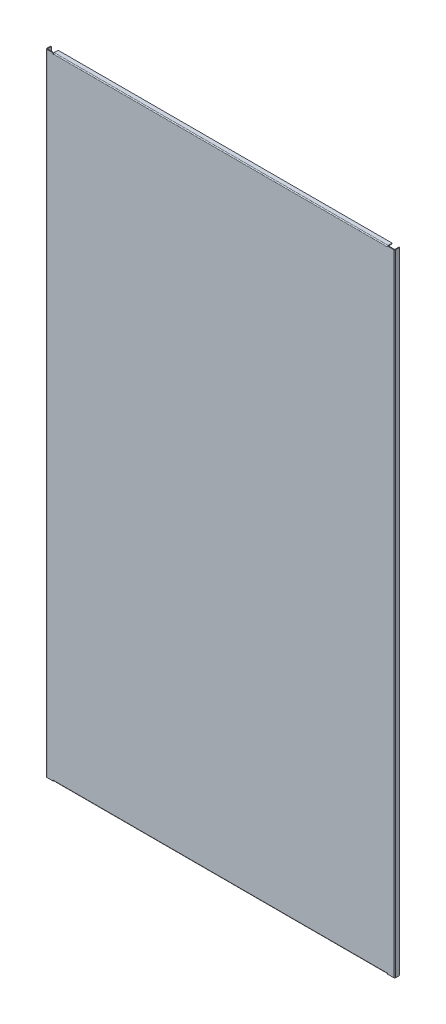
SolidWorks part; units mm, degrees
note: The reader was unsure of these and kept them because the rebuilt part matched: flange length of "Ребро-кромка1", "Ребро-кромка2".
material "AISI 1020"
ref_plane "Спереди" through (0, 0, 0) normal (0, 0, 1) x (1, 0, 0)
ref_plane "Сверху" through (0, 0, 0) normal (0, 1, 0) x (1, 0, 0)
ref_plane "Справа" through (0, 0, 0) normal (1, 0, 0) x (0, 0, -1)
sketch "Эскиз1" plane through (0, 0, 0) normal (0, 0, 1) x (1, 0, 0)
  line L0 (-540, 975) -> (540, 975) construction
  line L1 (-538.5, -973.5) -> (538.5, -973.5)
  line L2 (-538.5, -973.5) -> (-538.5, 973.5)
  line L3 (-538.5, 973.5) -> (538.5, 973.5)
  line L4 (538.5, -973.5) -> (538.5, 973.5)
  line L5 (-538.5, -973.5) -> (538.5, 973.5) construction
  line L6 (-538.5, 973.5) -> (538.5, -973.5) construction
  line L7 (-540, -1025) -> (-540, 1025) construction
  point P0 (0, 0)
  dimension "D1" = 1.5
  dimension "D2" = 1.5
base flange "Базовая кромка1" sketch "Эскиз1" thickness 2 reverse thickness direction yes parameters "D1"=0.75
edge flange "Ребро-кромка1" sketch "Эскиз10" flange profiles "Эскиз10", "Эскиз11" flange angle 90 flange length 15 flange position material inside bend radius 0.75 thickness 2 relief rectangular parameters "D6"=10, "D8"=1
sketch "Эскиз10" plane through (-538.5, 0, 0) normal (-1, 0, 0) x (0, 1, 0)
  line L2 (-973.5, 0) -> (-973.5, 13)
  line L3 (-973.5, 13) -> (973.5, 13)
  line L4 (973.5, 13) -> (973.5, 0)
  line L7 (973.5, 0) -> (-973.5, 0) construction
  line L8 (973.5, 0) -> (-973.5, 0)
sketch "Эскиз11" plane through (538.5, 0, 0) normal (1, 0, 0) x (0, -1, 0)
  line L0 (973.5, 0) -> (-973.5, 0) construction
  line L1 (973.5, 0) -> (-973.5, 0)
  line L2 (-973.5, 0) -> (-973.5, 13)
  line L3 (-973.5, 13) -> (973.5, 13)
  line L4 (973.5, 13) -> (973.5, 0)
bend "EdgeBend1" bend radius 0.75 bend angle 90 parameters "D5"=1
bend "EdgeBend2" bend radius 0.75 bend angle 90 parameters "D5"=2
edge flange "Ребро-кромка2" sketch "Эскиз16" flange profiles "Эскиз16", "Эскиз17" flange angle 90 flange length 15 flange position material inside bend radius 0.75 thickness 2 relief rectangular parameters "D6"=10, "D8"=1
sketch "Эскиз16" plane through (0, 973.5, 0) normal (0, 1, 0) x (1, 0, 0)
  line L2 (-515.75, 0) -> (-515.75, 13)
  line L3 (-515.75, 13) -> (515.75, 13)
  line L4 (515.75, 13) -> (515.75, 0)
  line L8 (515.75, 0) -> (-515.75, 0)
  line L9 (-535.75, -2) -> (-535.75, 0) construction
  line L10 (535.75, 0) -> (-535.75, 0) construction
  line L11 (-538.5, 13) -> (-536.5, 13) construction
  point P4 (0, 0)
  point P5 (-529.7554, 2.8927)
  point P10 (0, 0)
  point P11 (0, 0)
  dimension "D1" = 20
sketch "Эскиз17" plane through (0, -973.5, 0) normal (0, -1, 0) x (-1, 0, 0)
  line L1 (515.75, 0) -> (-515.75, 0)
  line L2 (-515.75, 0) -> (-515.75, 13)
  line L3 (-515.75, 13) -> (515.75, 13)
  line L4 (515.75, 13) -> (515.75, 0)
  line L6 (-535.75, -2) -> (-535.75, 0) construction
  line L7 (-538.5, 13) -> (-536.5, 13) construction
  line L8 (535.75, 0) -> (-535.75, 0) construction
  point P4 (-529.2306, 2.7321)
  point P5 (-511.7182, 2.9386)
  point P7 (-519.0256, 13.4638)
  point P13 (0, 0)
  point P14 (0, 0)
  dimension "D1" = 20
bend "EdgeBend3" bend radius 0.75 bend angle 90 parameters "D5"=3
bend "EdgeBend4" bend radius 0.75 bend angle 90 parameters "D5"=4
sketch "Сгиб-Линии1" plane through (0, 0, 0) normal (0, 1, 0) x (1, 0, 0)
sketch "Граничная рамка1" plane through (0, 0, 0) normal (0, 1, 0) x (1, 0, 0)
sheet metal parameters "Листовой металл3" thickness 2 parameters "D1"=0.75
flat pattern "Развертка3" [suppressed]
sketch "Сгиб-Линии2" plane through (0, 0, 0) normal (0, 1, 0) x (1, 0, 0)
sketch "Граничная рамка2" [suppressed] plane through (0, 0, 0) normal (0, 1, 0) x (1, 0, 0)
sheet metal parameters "Листовой металл4" thickness 2 parameters "D1"=0.75
flat pattern "Развертка3" [suppressed]
sketch "Сгиб-Линии2" plane through (0, 0, 0) normal (0, 1, 0) x (1, 0, 0)
sketch "Граничная рамка2" [suppressed] plane through (0, 0, 0) normal (0, 1, 0) x (1, 0, 0)
bend of the flat pattern "Плоское состояние-<EdgeBend1>1"
bend of the flat pattern "Плоское состояние-<EdgeBend2>1"
sheet metal parameters "Листовой металл5" thickness 2 parameters "D1"=0.75
flat pattern "Развертка3" [suppressed]
sketch "Сгиб-Линии2" plane through (0, 0, 0) normal (0, 1, 0) x (1, 0, 0)
sketch "Граничная рамка2" [suppressed] plane through (0, 0, 0) normal (0, 1, 0) x (1, 0, 0)
bend of the flat pattern "Плоское состояние-<EdgeBend1>1"
bend of the flat pattern "Плоское состояние-<EdgeBend2>1"
bend of the flat pattern "Плоское состояние-<EdgeBend3>1"
bend of the flat pattern "Плоское состояние-<EdgeBend4>1"
